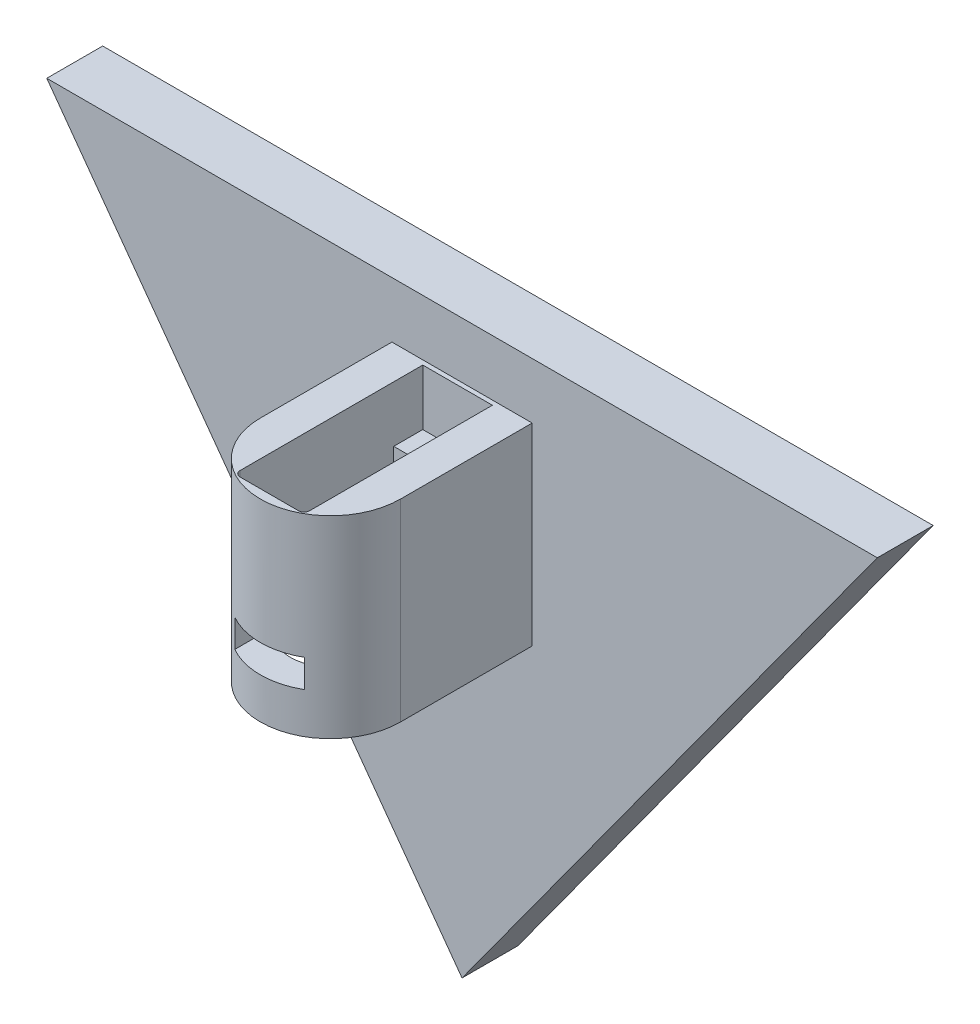
SolidWorks part; units mm, degrees
ref_plane "Front Plane" through (0, 0, 0) normal (0, 0, 1) x (1, 0, 0)
ref_plane "Top Plane" through (0, 0, 0) normal (0, 1, 0) x (1, 0, 0)
ref_plane "Right Plane" through (0, 0, 0) normal (1, 0, 0) x (0, 0, -1)
sketch "Sketch4" plane through (0, 0, 0) normal (0, 0, 1) x (1, 0, 0)
  line L0 (55, 0) -> (-55, 0) construction
  line L1 (-6.23, -9.975) -> (6.23, -9.975)
  line L2 (-6.23, -9.975) -> (-6.23, 7.275)
  line L3 (-6.23, 7.275) -> (6.23, 7.275)
  line L4 (6.23, -9.975) -> (6.23, 7.275)
  point P4 (0, 7.275)
  dimension "D1" = 12.46
  dimension "D2" = 17.25
  dimension "D3" = 9.975
extrude "Boss-Extrude3" add sketch "Sketch4" along normal blind 6
sketch "Sketch8" plane through (0, -9.975, 0) normal (0, -1, 0) x (-1, 0, 0)
  circle A0 centre (0, -23.55) radius 12.5468
  circle A1 centre (0, -23.55) radius 11.15
  dimension "D1" = 22.3
  dimension "D2" = 23.55
extrude "Boss-Extrude6" add sketch "Sketch8" along normal blind 7.3 and the other way up to surface (17.25 mm away) other way up to face at (0, 7.275, 3)
sketch "Sketch5" plane through (0, 7.275, 0) normal (0, 1, 0) x (1, 0, 0)
  line L8 (12.5468, -23.55) -> (12.5468, 0)
  line L9 (12.5468, 0) -> (6.23, 0)
  line L10 (-12.5468, -23.55) -> (-12.5468, 0)
  line L11 (-12.5468, 0) -> (-6.23, 0)
  line L12 (-6.23, 0) -> (-6.23, -29.7)
  line L14 (6.23, -29.7) -> (6.23, 0)
  line L15 (-6.23, -29.7) -> (6.23, -29.7)
  line L16 (6.23, -6) -> (-6.23, -6) construction
  circle A0 centre (0, -23.55) radius 12.5468 construction
  arc A1 (-12.5468, -23.55) -> (12.5468, -23.55) centre (0, -23.55) ccw
  dimension "D1" = 23.7
  dimension "D2" = 23.55
extrude "Boss-Extrude4" add sketch "Sketch5" against normal up to surface (17.25 mm away) up to face at (0, -9.975, 3)
sketch "Sketch6" plane through (0, 7.275, 0) normal (0, 1, 0) x (1, 0, 0)
  line L0 (6.23, -6) -> (-6.23, -6) construction
  line L3 (6.23, -29.7) -> (-6.23, -29.7) construction
  circle A0 centre (0, -3.6) radius 0.5
  circle A1 centre (0, -32.1) radius 0.5
  dimension "D1" = 1
  dimension "D3" = 1
  dimension "D2" = 2.4
  dimension "D4" = 2.4
extrude "Cut-Extrude1" cut sketch "Sketch6" against normal blind 5
chamfer "Chamfer1" distance 0.5 angle 60 2 edges at (0, 7.275, 4.1) (0, 7.275, 32.6) first distance on face at (0, 7.275, 4.1)
sketch "Sketch10" plane through (0, 7.275, 0) normal (0, 1, 0) x (1, 0, 0)
  line L1 (-6.23, -6) -> (6.23, -6)
  line L2 (-6.23, -6) -> (-6.23, -29.7)
  line L3 (-6.23, -29.7) -> (6.23, -29.7)
  line L4 (6.23, -6) -> (6.23, -29.7)
extrude "Cut-Extrude3" cut sketch "Sketch10" against normal up to surface (17.25 mm away) up to face at (0, -9.975, 27.1007)
ref_plane "Plane1" through (0, 0, 36.0968) normal (0, 0, 1) x (1, 0, 0)
sketch "Sketch11" plane through (0, 0, 36.0968) normal (0, 0, 1) x (1, 0, 0)
  line L0 (-11.15, -9.975) -> (11.15, -9.975) construction
  line L1 (-6.23, -4.975) -> (6.23, -4.975)
  line L2 (-6.23, -4.975) -> (-6.23, -9.975)
  line L3 (-6.23, -9.975) -> (6.23, -9.975)
  line L4 (6.23, -4.975) -> (6.23, -9.975)
  line L5 (6.23, -9.975) -> (6.23, 7.275) construction
  point P4 (0, -4.975)
  dimension "D1" = 0
  dimension "D2" = 0
  dimension "D3" = 5
extrude "Cut-Extrude4" cut sketch "Sketch11" against normal up to next
sketch "Sketch13" plane through (0, -17.275, 0) normal (0, -1, 0) x (1, 0, 0)
  line L0 (-12.5468, 23.55) -> (-12.5468, 0)
  line L1 (-12.5468, 0) -> (12.5468, 0)
  line L2 (12.5468, 0) -> (12.5468, 23.55)
  arc A0 (-12.5468, 23.55) -> (12.5468, 23.55) centre (0, 23.55) ccw
  point P3 (0, 0)
extrude "Boss-Extrude7" add sketch "Sketch13" against normal up to surface (7.3 mm away) up to face at (8.69, -9.975, 23.55)
sketch "Sketch15" plane through (0, 7.275, 0) normal (0, 1, 0) x (1, 0, 0)
  line L0 (-12.5468, 0) -> (12.5468, 0)
  line L1 (12.5468, 0) -> (12.5468, -23.55)
  line L2 (-12.5468, 0) -> (-12.5468, -23.55)
  line L3 (6.23, -6) -> (6.23, -29.7) construction
  line L4 (-6.23, -0.8) -> (6.23, -0.8)
  line L5 (-6.23, -0.8) -> (-6.23, -33.5)
  line L6 (-5.23, -34.5) -> (5.23, -34.5)
  line L7 (6.23, -0.8) -> (6.23, -33.5)
  arc A0 (-12.5468, -23.55) -> (12.5468, -23.55) centre (0, -23.55) ccw
  circle A1 centre (0, -3.6) radius 0.5 construction
  arc A2 (5.23, -34.5) -> (6.23, -33.5) centre (5.23, -33.5) ccw
  arc A3 (-6.23, -33.5) -> (-5.23, -34.5) centre (-5.23, -33.5) ccw
  point P15 (0, -0.8)
  dimension "D1" = 0.8
  dimension "D3" = 1
  dimension "D2" = 2.8
  dimension "D4" = 0
  dimension "D5" = 34.5
extrude "Boss-Extrude9" add sketch "Sketch15" along normal blind 10
sketch "Sketch16" plane through (0, -17.275, 0) normal (0, -1, 0) x (1, 0, 0)
  circle A0 centre (0, 23.55) radius 11.15
  circle A1 centre (0, 23.55) radius 7.15
  circle A2 centre (0, 23.55) radius 11.15 construction
  dimension "D1" = 14.3
extrude "Boss-Extrude10" add sketch "Sketch16" against normal up to surface (7.3 mm away) up to face at (8.69, -9.975, 23.55)
sketch "Sketch17" plane through (0, -17.275, 0) normal (0, -1, 0) x (1, 0, 0)
  circle A0 centre (0, 23.55) radius 10.15
  circle A1 centre (0, 23.55) radius 7.15
  circle A2 centre (0, 23.55) radius 7.15 construction
  dimension "D1" = 20.3
extrude "Cut-Extrude5" cut sketch "Sketch17" against normal blind 1.3
sketch "Sketch1" plane through (0, 0, 0) normal (0, 0, 1) x (1, 0, 0)
  line L0 (0, -75) -> (74.3071, 27.275)
  line L1 (74.3071, 27.275) -> (-74.3071, 27.275)
  line L2 (-74.3071, 27.275) -> (0, -75)
  line L3 (6.23, 17.275) -> (-6.23, 17.275) construction
  line L4 (13.8015, 0) -> (-13.8015, 0) construction
  point P10 (0, 27.275)
  dimension "D2" = 10
  dimension "D1" = 72
  dimension "D3" = 75
extrude "Offset R" add sketch "Sketch1" against normal blind 10 contours L2 L0 L1
